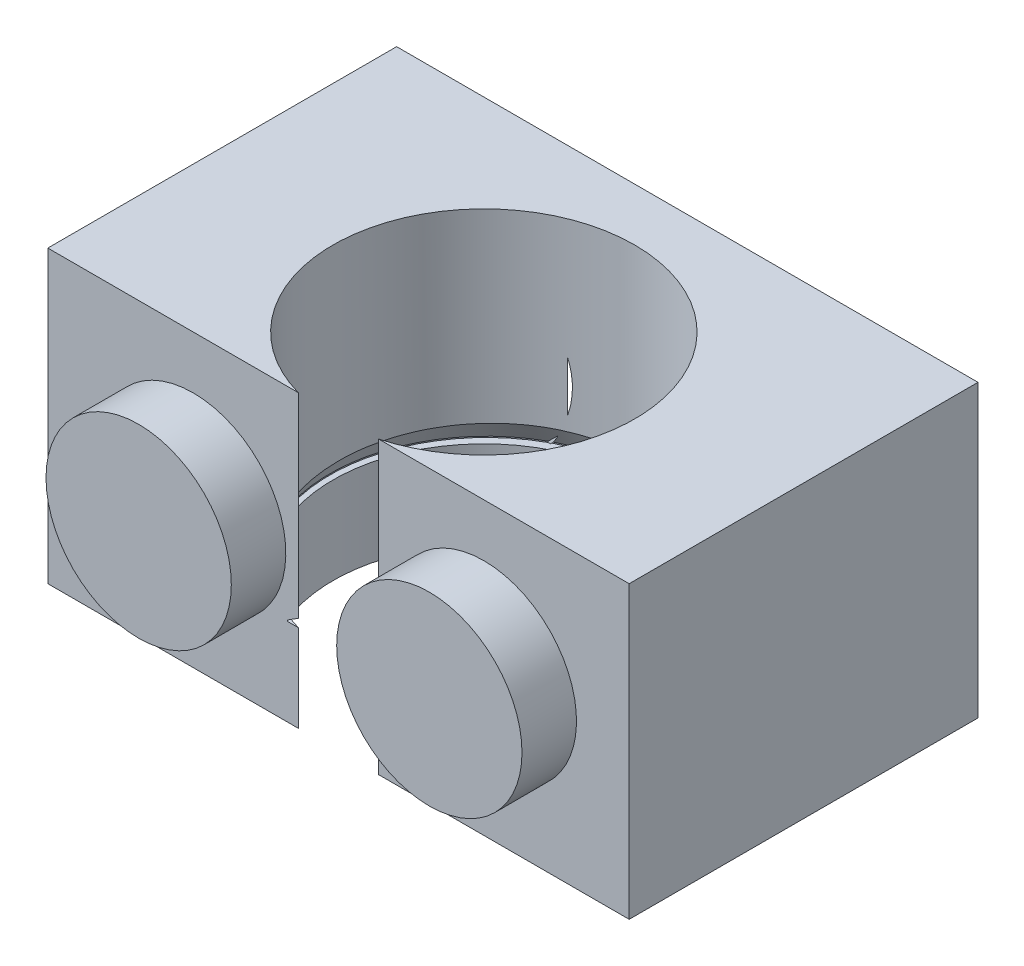
SolidWorks part; units mm, degrees
material "ABS"
ref_plane "Front Plane" through (0, 0, 0) normal (0, 0, 1) x (1, 0, 0)
ref_plane "Top Plane" through (0, 0, 0) normal (0, 1, 0) x (1, 0, 0)
ref_plane "Right Plane" through (0, 0, 0) normal (1, 0, 0) x (0, 0, -1)
sketch "Sketch1" plane through (0, -47.1987, 0) normal (0, 1, 0) x (1, 0, 0)
  line L0 (24, 8.8545) -> (8, 8.8545) construction
  line L1 (8, 18.4545) -> (24, 18.4545) construction
  line L2 (24, 8.8545) -> (8, 8.8545) construction
  line L3 (8, 18.4545) -> (24, 18.4545) construction
  line L5 (8, 8.8545) -> (24, 8.8545)
  line L6 (8, 8.8545) -> (8, 18.4545)
  line L7 (8, 18.4545) -> (24, 18.4545)
  line L8 (24, 8.8545) -> (24, 18.4545)
  circle A0 centre (16, 12.8545) radius 4 construction
  circle A1 centre (16, 12.8545) radius 4 construction
  circle A2 centre (16, 12.8545) radius 4.15
  circle M2 centre (16, 12.8545) radius 5.225
  dimension "D1" = 0.15
extrude "Boss-Extrude1" add sketch "Sketch1" along normal blind 8 contours L5 L8 L7 L6 M2 | A2 L5 M2 region at (8.1866, -47.1987, -13.6544) region at (13.8525, -47.1987, -17.4644)
ref_plane "Plane1" through (16, 0, 0) normal (-1, 0, 0) x (0, 0, 1)
sketch "Sketch2" plane through (16, 0, 0) normal (-1, 0, 0) x (0, 0, 1)
  line L0 (-17.0894, -44.7987) -> (-8.6194, -44.7987) construction
  line L2 (-14.2539, -44.2637) -> (-8.8544, -44.2637) construction
  line L3 (-17.0894, -44.7987) -> (-8.6194, -44.7987) construction
  line L4 (-8.8544, -39.1987) -> (-17.0044, -39.1987) construction
  line L5 (-14.2539, -44.2637) -> (-8.8544, -44.2637) construction
  line L6 (-8.8544, -44.2637) -> (-8.6194, -44.7677)
  line L7 (-8.6194, -44.7677) -> (-8.6194, -44.7987)
  line L8 (-8.8544, -44.2637) -> (-8.8544, -44.7987)
  line L9 (-8.6194, -44.7987) -> (-8.8544, -44.7987)
  line L14 (-12.9294, -46.259) -> (-12.9294, -50046.259) construction
  line L15 (-8.8544, -39.1987) -> (-17.0044, -39.1987) construction
  point P2 (-12.9294, -39.1987)
revolve "Cut-Revolve1" cut sketch "Sketch2" angle 360 about L14
sketch "Sketch3" plane through (0, 0, -8.8545) normal (0, 0, 1) x (1, 0, 0)
  circle A0 centre (20, -43.1987) radius 2.4 construction
  circle A1 centre (12, -43.1987) radius 2.4 construction
  circle A2 centre (20, -43.1987) radius 2.4 construction
  circle A3 centre (12, -43.1987) radius 2.4 construction
  circle A4 centre (12, -43.1987) radius 2.55
  circle A6 centre (20, -43.1987) radius 2.55
  dimension "D1" = 0.15
extrude "Boss-Extrude2" add sketch "Sketch3" along normal blind 1.5 contours A4 | A6 region at (12, -43.1987, -8.8544) region at (20, -43.1987, -8.8544)
extrude "Cut-Extrude1" cut sketch "Sketch3<3>" along normal blind 1.75 from surface contours A4 | A6 starting at face at (16, -43.1987, -18.4544)
sketch "Sketch3<3>" plane through (0, 0, -8.8545) normal (0, 0, 1) x (1, 0, 0) same geometry as "Sketch3"
